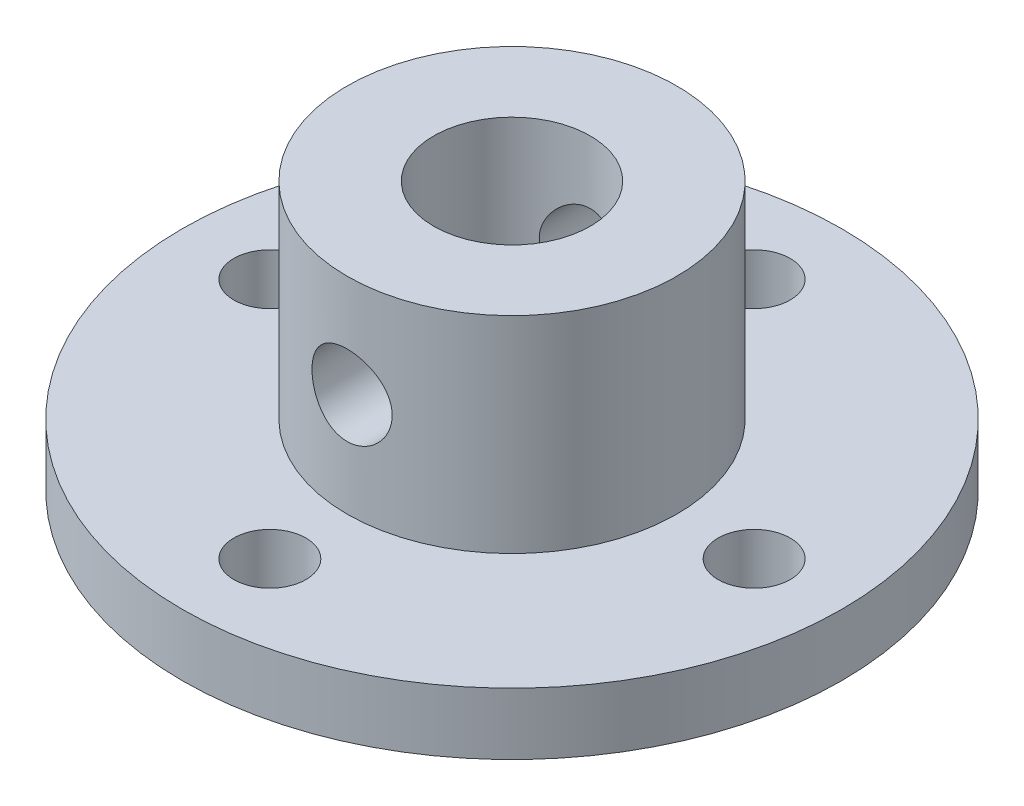
SolidWorks part; units mm, degrees
ref_plane "Front Plane" through (0, 0, 0) normal (0, 0, 1) x (1, 0, 0)
ref_plane "Top Plane" through (0, 0, 0) normal (0, 1, 0) x (1, 0, 0)
ref_plane "Right Plane" through (0, 0, 0) normal (1, 0, 0) x (0, 0, -1)
sketch "Sketch1" plane through (0, 0, 0) normal (0, 1, 0) x (1, 0, 0)
  circle A0 centre (0, 0) radius 16
  circle A1 centre (0, 0) radius 11.75 construction
  circle A2 centre (0, 0) radius 8
  circle A3 centre (0, 0) radius 3.8
  circle A4 centre (0, 11.75) radius 1.75
  circle A5 centre (11.75, 0) radius 1.75
  circle A6 centre (0, -11.75) radius 1.75
  circle A7 centre (-11.75, 0) radius 1.75
  point P17 (0, 0)
  dimension "D1" = 32
  dimension "D2" = 16
  dimension "D3" = 7.6
  dimension "D5" = 3.5
  dimension "D6" = 23.5
  dimension "D4" = 4
extrude "Boss-Extrude1" add sketch "Sketch1" along normal blind 3 contours A0 A7 A6 A5 A4 A2 region at (-15.5475, 0, 0)
extrude "Boss-Extrude2" add sketch "Sketch1<3>" along normal blind 13 contours A2 A3 region at (-7.7737, 0, 0)
sketch "Sketch1<3>" plane through (0, 0, 0) normal (0, 1, 0) x (1, 0, 0) same geometry as "Sketch1"
sketch "Sketch2" plane through (0, 0, 0) normal (0, 0, 1) x (1, 0, 0)
  line L0 (3.8, 13) -> (-3.8, 13) construction
  circle A0 centre (0, 8) radius 1.9443
  dimension "D1" = 5
extrude "Cut-Extrude1" cut sketch "Sketch2" against normal through all both and the other way through all
